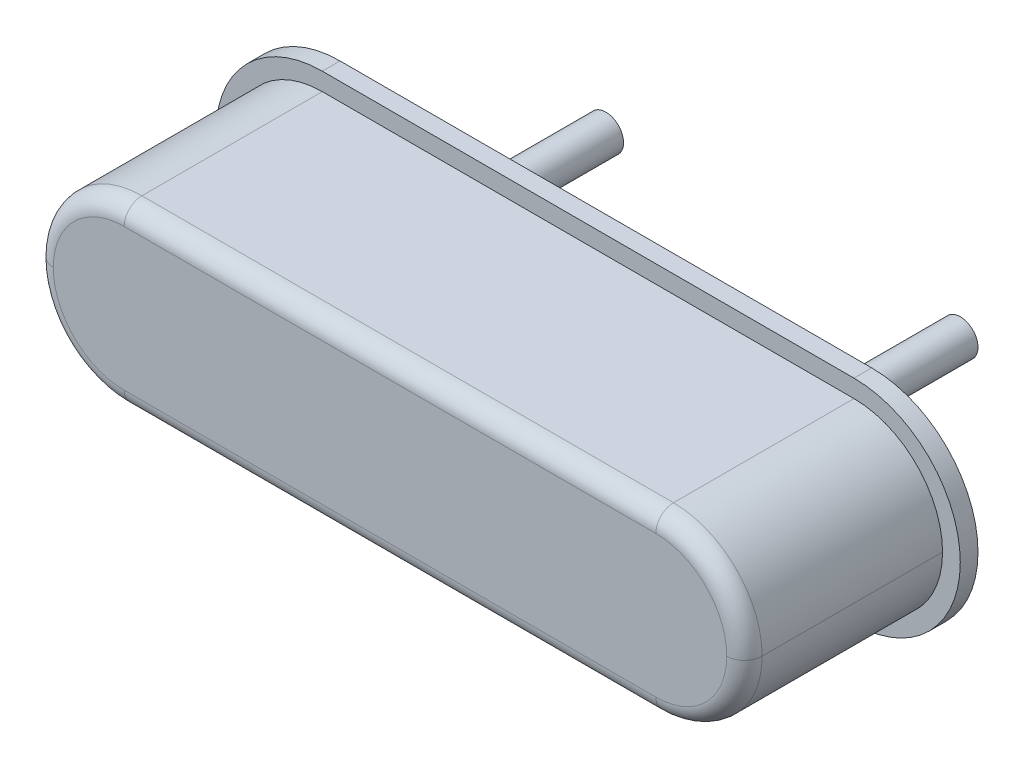
SolidWorks part; units mm, degrees
ref_plane "x/y" through (0, 0, 0) normal (0, 0, 1) x (1, 0, 0)
ref_plane "x/z" through (0, 0, 0) normal (0, 1, 0) x (1, 0, 0)
ref_plane "y/z" through (0, 0, 0) normal (1, 0, 0) x (0, 0, -1)
sketch "Sketch1" plane through (0, 0, 0) normal (0, 1, 0) x (1, 0, 0)
  line L0 (0, 2.54) -> (0, -0.508)
ref_plane "Plane4" through (0, 0, -2.54) normal (0, 0, 1) x (1, 0, 0)
sketch "Sketch2" plane through (0, 0, -2.54) normal (0, 0, 1) x (1, 0, 0)
  circle A0 centre (0, 0) radius 0.254
sweep "Base-Sweep" add profiles "Sketch2" path "Sketch1"
sketch "Sketch4" plane through (0, 0, 0) normal (0, 1, 0) x (1, 0, 0)
  line L0 (-2.54, 0) -> (7.62, 0)
  line L1 (-2.54, 0) -> (-2.54, -3.0936)
  line L2 (7.62, -3.0936) -> (-2.54, -3.0936)
  line L3 (7.62, -3.0936) -> (7.62, 0)
extrude "Boss-Extrude1" add sketch "Sketch4" along normal mid plane 2.54
fillet "Fillet1" radius 1.27 8 edges at (7.62, 0, 0) (-2.54, -1.27, 1.5468) (-2.54, 0, 0) (-2.54, 0, 3.0936) (7.62, -1.27, 1.5468) (7.62, 0, 3.0936) (-2.54, 1.27, 1.5468) (7.62, 1.27, 1.5468)
fillet "Fillet2" radius 0.254 6 edges at (2.54, 1.27, 3.0936) (7.248, 0.898, 3.0936) (7.248, -0.898, 3.0936) (2.54, -1.27, 3.0936) (-2.168, -0.898, 3.0936) (-2.168, 0.898, 3.0936)
ref_plane "Plane10" through (2.54, 0, 0) normal (1, 0, 0) x (0, 0, -1)
mirror "Mirror5" about plane through (2.54, 0, 0) normal (1, 0, 0) of "Base-Sweep"
sketch "Sketch6" plane through (0, 0, 0) normal (0, 0, -1) x (-1, 0, 0)
  line L2 (-6.35, -1.524) -> (1.27, -1.524)
  line L3 (1.27, 1.524) -> (-6.35, 1.524)
  line L4 (-6.35, -1.524) -> (1.27, -1.524)
  line L5 (1.27, 1.524) -> (-6.35, 1.524)
  arc A4 (1.27, -1.524) -> (2.794, 0) centre (1.27, 0) ccw
  arc A5 (2.794, 0) -> (1.27, 1.524) centre (1.27, 0) ccw
  arc A6 (-6.35, 1.524) -> (-7.874, 0) centre (-6.35, 0) ccw
  arc A7 (-7.874, 0) -> (-6.35, -1.524) centre (-6.35, 0) ccw
  arc A8 (1.27, -1.524) -> (2.794, 0) centre (1.27, 0) ccw
  arc A9 (2.794, 0) -> (1.27, 1.524) centre (1.27, 0) ccw
  arc A10 (-6.35, 1.524) -> (-7.874, 0) centre (-6.35, 0) ccw
  arc A11 (-7.874, 0) -> (-6.35, -1.524) centre (-6.35, 0) ccw
  dimension "D1" = 0.254
extrude "Boss-Extrude2" add sketch "Sketch6" against normal blind 0.254
